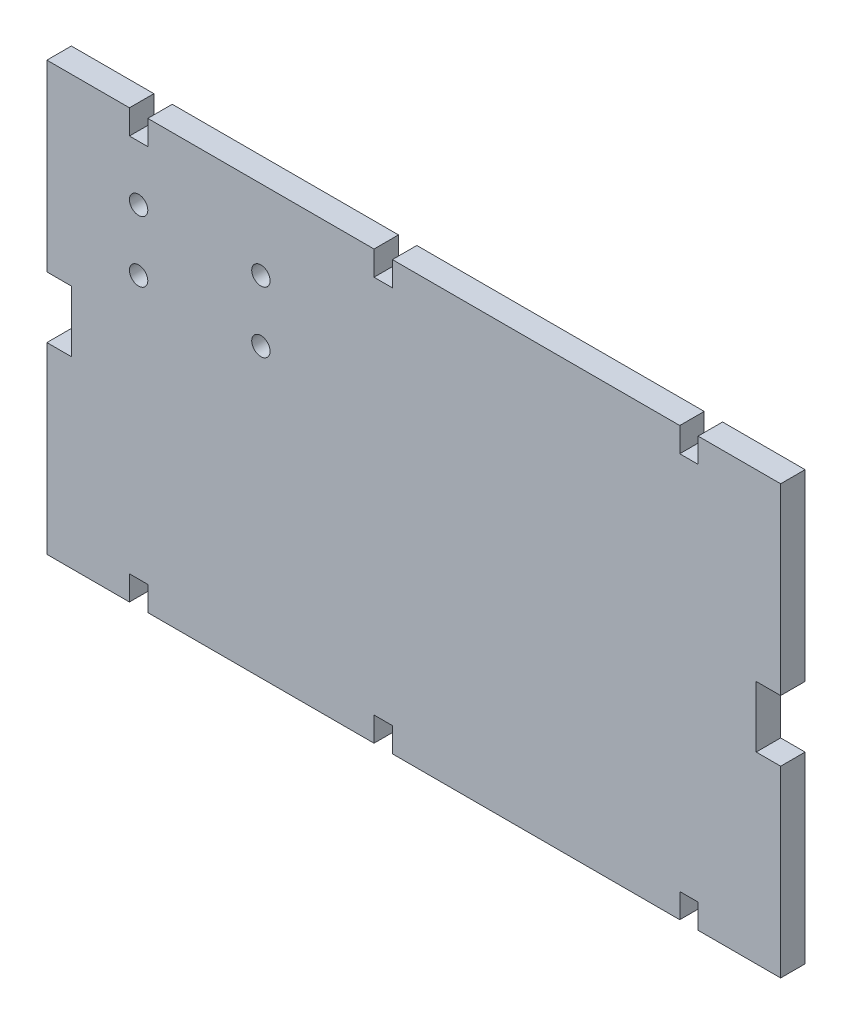
SolidWorks part; units mm, degrees
ref_plane "Front Plane" through (0, 0, 0) normal (0, 0, 1) x (1, 0, 0)
ref_plane "Top Plane" through (0, 0, 0) normal (0, 1, 0) x (1, 0, 0)
ref_plane "Right Plane" through (0, 0, 0) normal (1, 0, 0) x (0, 0, -1)
sketch "Sketch1" plane through (0, 0, 0) normal (0, 0, 1) x (1, 0, 0)
  line L1 (0, 0) -> (120, 0)
  line L2 (0, 0) -> (0, 70)
  line L3 (0, 70) -> (120, 70)
  line L4 (120, 0) -> (120, 70)
  dimension "D1" = 120
  dimension "D2" = 70
extrude "Boss-Extrude1" add sketch "Sketch1" along normal blind 4
sketch "Sketch2" plane through (0, 0, 4) normal (0, 0, 1) x (1, 0, 0)
  line L0 (120, 0) -> (120, 70) construction
  line L1 (120, 40) -> (116, 40)
  line L2 (120, 40) -> (120, 30)
  line L3 (120, 30) -> (116, 30)
  line L4 (116, 40) -> (116, 30)
  line L5 (120, 70) -> (0, 70) construction
  line L6 (13.5, 70) -> (16.5, 70)
  line L7 (13.5, 70) -> (13.5, 66)
  line L8 (13.5, 66) -> (16.5, 66)
  line L9 (16.5, 70) -> (16.5, 66)
  line L10 (15, 66) -> (15, 58.709) construction
  line L11 (53.5, 70) -> (56.5, 70)
  line L12 (53.5, 70) -> (53.5, 66)
  line L13 (53.5, 66) -> (56.5, 66)
  line L14 (56.5, 70) -> (56.5, 66)
  line L15 (103.5, 70) -> (106.5, 70)
  line L16 (103.5, 70) -> (103.5, 66)
  line L17 (103.5, 66) -> (106.5, 66)
  line L18 (106.5, 70) -> (106.5, 66)
  line L19 (55, 66) -> (55, 57.8934) construction
  line L20 (105, 66) -> (105, 57.8934) construction
  line L21 (0, 70) -> (0, 0) construction
  line L22 (0, 0) -> (120, 0) construction
  line L23 (0, 40) -> (4, 40)
  line L24 (0, 40) -> (0, 30)
  line L25 (0, 30) -> (4, 30)
  line L26 (4, 40) -> (4, 30)
  line L28 (105, 4) -> (105, 12.1066) construction
  line L29 (55, 4) -> (55, 12.1066) construction
  line L30 (15, 4) -> (15, 11.291) construction
  line L31 (0, 30) -> (4, 30)
  line L32 (106.5, 0) -> (106.5, 4)
  line L33 (103.5, 4) -> (106.5, 4)
  line L34 (103.5, 0) -> (103.5, 4)
  line L35 (103.5, 0) -> (106.5, 0)
  line L36 (56.5, 0) -> (56.5, 4)
  line L37 (53.5, 4) -> (56.5, 4)
  line L38 (53.5, 0) -> (53.5, 4)
  line L39 (53.5, 0) -> (56.5, 0)
  line L40 (16.5, 0) -> (16.5, 4)
  line L41 (13.5, 4) -> (16.5, 4)
  line L42 (13.5, 0) -> (13.5, 4)
  line L43 (13.5, 0) -> (16.5, 0)
  line L44 (120, 30) -> (116, 30)
  line M15 (0, 70) -> (0, 0)
  line M16 (0, 0) -> (120, 0)
  line M17 (120, 0) -> (120, 70)
  line M18 (120, 70) -> (0, 70)
  dimension "D1" = 3
  dimension "D2" = 4
  dimension "D3" = 15
  dimension "D4" = 55
  dimension "D5" = 15
  dimension "D6" = 10
  dimension "D7" = 10
  dimension "D8" = 4
  dimension "D9" = 30
  dimension "D10" = 30
extrude "Cut-Extrude1" cut sketch "Sketch2" against normal blind 4 contours L42 L40 L41 M16 | L26 L23 L25 M15 | L14 L12 L13 M18 | L18 L16 L17 M18 | L1 L4 L3 M17 | L34 L32 L33 M16 | L38 L36 L37 M16 | L7 L8 L9 L6 region at (118, 35, 4) region at (105, 68, 4) region at (105, 2, 4) region at (55, 68, 4) region at (55, 2, 4) region at (15, 2, 4) region at (2, 35, 4)
sketch "Sketch3" plane through (0, 0, 4) normal (0, 0, 1) x (1, 0, 0)
  line L0 (25, 40.5) -> (25, 17.0361) construction
  line L1 (15, 40.5) -> (35, 40.5) construction
  line L2 (15, 40.5) -> (15, 29.5) construction
  line L3 (15, 29.5) -> (35, 29.5) construction
  line L4 (35, 40.5) -> (35, 29.5) construction
  line L5 (0, 30) -> (0, 0) construction
  line L6 (4, 35) -> (70.4442, 35) construction
  line L7 (4, 40) -> (4, 30) construction
  line L8 (35, 35) -> (101.4442, 35) construction
  line L10 (19, 43.7731) -> (31, 43.7731) construction
  line L11 (19, 43.7731) -> (19, 65.7731) construction
  line L12 (19, 65.7731) -> (31, 65.7731) construction
  line L13 (31, 43.7731) -> (31, 65.7731) construction
  line L14 (19, 43.7731) -> (31, 65.7731) construction
  line L15 (19, 65.7731) -> (31, 43.7731) construction
  circle A0 centre (35, 47) radius 1.5
  circle A1 centre (35, 57) radius 1.5
  circle A2 centre (15, 57) radius 1.5
  circle A3 centre (15, 47) radius 1.5
  point P14 (25, 54.7731)
  point P23 (0, 0)
  point P24 (0, 0)
  point P25 (0, 0)
  dimension "D6" = 10
  dimension "D7" = 3
  dimension "D8" = 10
  dimension "D1" = 25
  dimension "D2" = 11
  dimension "D3" = 20
  dimension "D4" = 22
  dimension "D5" = 12
  dimension "D9" = 12
extrude "Cut-Extrude2" cut sketch "Sketch3" against normal blind 4
